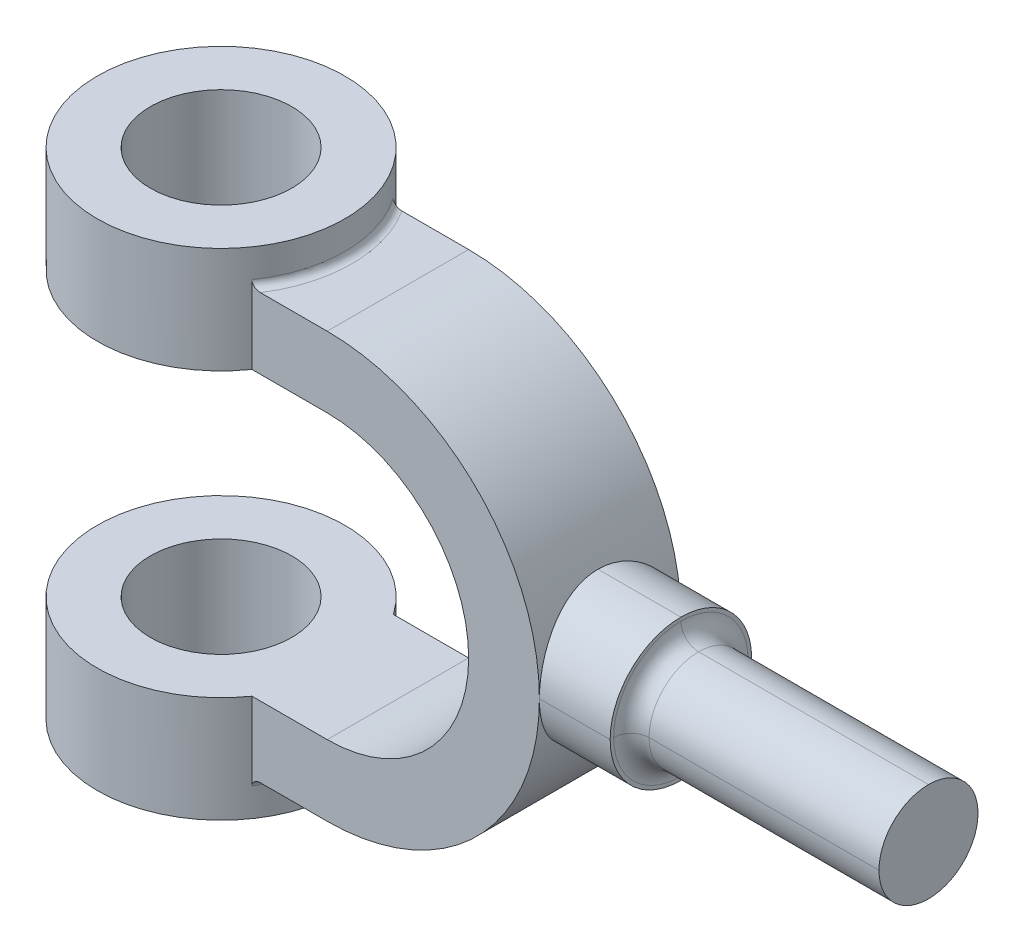
SolidWorks part; units mm, degrees
ref_plane "Front Plane" through (0, 0, 0) normal (0, 0, 1) x (1, 0, 0)
ref_plane "Top Plane" through (0, 0, 0) normal (0, 1, 0) x (1, 0, 0)
ref_plane "Right Plane" through (0, 0, 0) normal (1, 0, 0) x (0, 0, -1)
sketch "Sketch3" plane through (0, 0, 0) normal (0, 1, 0) x (1, 0, 0)
  line L0 (0, 96.7811) -> (0, -101.4807) construction
  line L1 (-123.3629, 0) -> (83.1231, 0) construction
  circle A0 centre (0, 0) radius 20
  circle A1 centre (0, 0) radius 35
  dimension "D1" = 70
  dimension "D2" = 40
extrude "Boss-Extrude1" add sketch "Sketch3" along normal blind 30
ref_plane "Plane1" through (0, -40, 0) normal (0, 1, 0) x (1, 0, 0)
pattern_linear "LPattern2" count 2 spacing 110 along (0, 1, 0) of bodies 101
ref_axis "Axis1" through (0, 140, 0) along (0, -1, 0)
ref_plane "Plane2" through (0, 0, 0) normal (0, 0, 1) x (0, -1, 0)
sketch "Sketch5" plane through (0, 0, 0) normal (0, 0, 1) x (0, -1, 0)
  line L0 (0, 0) -> (-36.8338, 0) construction
  line L1 (-103.1662, 0) -> (-50000, 0) construction
  line L2 (-70, 87.1885) -> (-70, -47.3376)
  line L3 (-110, -35) -> (-110, 35) construction
  line L4 (-10, 21.3) -> (-10, 50)
  line L5 (-110, 21.3) -> (-130, 21.3)
  line L6 (-110, 21.3) -> (-110, 50)
  line L8 (-130, 21.3) -> (-130, 50)
  line L10 (-30, 21.3) -> (-30, 50)
  line L11 (-30, 21.3) -> (-10, 21.3)
  arc A0 (-30, 50) -> (-110, 50) centre (-70, 50) ccw
  arc A2 (-10, 50) -> (-130, 50) centre (-70, 50) ccw
  dimension "D6" = 80
  dimension "D1" = 40
  dimension "D2" = 28.7
  dimension "D4" = 21.3
  dimension "D5" = 50
extrude "Boss-Extrude2" add sketch "Sketch5" along normal blind 20 and the other way blind 20 contours L4 A2 L8 L5 L6 A0 L10 L11 region at (22.7922, 20, 0)
fillet "Fillet1" radius 2 2 edges at (35, 10, 0) (35, 130, 0)
sketch "Sketch6" plane through (0, 0, 0) normal (0, 0, 1) x (0, -1, 0)
  line L0 (-90, 130) -> (-90, 100)
  line L1 (-90, 100) -> (-50, 100)
  line L2 (-50, 100) -> (-50, 130)
  line L3 (-50, 130) -> (-90, 130)
  line L4 (-84, 130) -> (-84, 200)
  line L5 (-84, 200) -> (-56, 200)
  line L6 (-56, 200) -> (-56, 130)
  line L7 (-170.2341, 0) -> (23.5045, 0)
  line L8 (-70, -29.1999) -> (-70, 34.8736)
  line L9 (-110, -35) -> (-110, 28.7228) construction
  line L10 (-56, 130) -> (-84, 130)
  line L11 (-30, 28.7228) -> (-30, -35) construction
  point P15 (-70, 100)
  dimension "D1" = 40
  dimension "D2" = 40
  dimension "D3" = 130
  dimension "D4" = 100
  dimension "D5" = 26
  dimension "D6" = 40
  dimension "D7" = 26
  dimension "D8" = 70
extrude "Boss-Extrude3" add sketch "Sketch6" along normal blind 20 and the other way blind 20 contours L2 L3 L0 L1 region at (115, 70, 0)
extrude "Boss-Extrude4" add sketch "Sketch6<3>" along normal blind 14 and the other way blind 14 contours L6 L5 L4 L3 region at (165, 70, 0)
sketch "Sketch6<3>" plane through (0, 0, 0) normal (0, 0, 1) x (0, -1, 0) same geometry as "Sketch6"
fillet "Fillet2" radius 14 4 edges at (165, 56, -14) (165, 56, 14) (165, 84, 14) (165, 84, -14)
fillet "Fillet3" radius 20 4 edges at (118.2843, 50, -20) (118.2843, 50, 20) (118.2843, 90, 20) (118.2843, 90, -20)
fillet "Fillet4" radius 5 4 edges at (130, 79.8995, -9.8995) (130, 79.8995, 9.8995) (130, 60.1005, 9.8995) (130, 60.1005, -9.8995)
